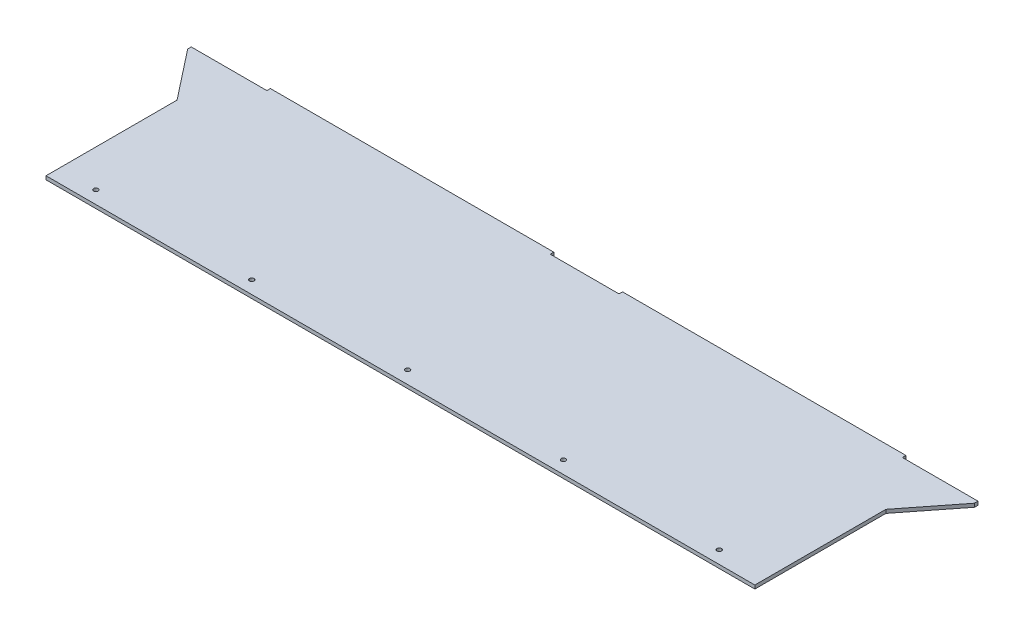
SolidWorks part; units mm, degrees
material "6061-T6 (SS)"
ref_plane "X-Y Datum" through (0, 0, 0) normal (0, 0, 1) x (1, 0, 0)
ref_plane "X-Z Datum" through (0, 0, 0) normal (0, 1, 0) x (1, 0, 0)
ref_plane "Y-Z Datum" through (0, 0, 0) normal (1, 0, 0) x (0, 0, -1)
sketch "Sketch1" plane through (0, 0, 0) normal (0, 1, 0) x (1, 0, 0)
  line L1 (-317.6778, 82.55) -> (317.6778, 82.55)
  line L2 (-317.6778, 82.55) -> (-317.6778, -82.55)
  line L3 (-317.6778, -82.55) -> (317.6778, -82.55)
  line L4 (317.6778, 82.55) -> (317.6778, -82.55)
  line L5 (-317.6778, 82.55) -> (317.6778, -82.55) construction
  line L6 (-317.6778, -82.55) -> (317.6778, 82.55) construction
  point P0 (0, 0)
  dimension "D1" = 635.3556
  dimension "D2" = 165.1
extrude "Boss-Extrude1" add sketch "Sketch1" along normal mid plane 3.175
sketch "Sketch2" plane through (0, 0, -82.55) normal (0, 0, -1) x (-1, 0, 0)
  line L20 (-317.6778, -1.5875) -> (317.6778, -1.5875) construction
  line L21 (-284.8229, -1.5875) -> (-30.8229, -1.5875)
  line L22 (30.8229, -1.5875) -> (284.8229, -1.5875)
  line L40 (30.8229, -1.5875) -> (30.8229, 1.5875)
  line L41 (30.8229, 1.5875) -> (284.8229, 1.5875)
  line L42 (284.8229, 1.5875) -> (284.8229, -1.5875)
  line L56 (-284.8229, -1.5875) -> (-284.8229, 1.5875)
  line L57 (-284.8229, 1.5875) -> (-30.8229, 1.5875)
  line L58 (-30.8229, 1.5875) -> (-30.8229, -1.5875)
extrude "Boss-Extrude2" add sketch "Sketch2" along normal blind 3.175
sketch "Sketch3" plane through (0, -1.5875, 0) normal (0, -1, 0) x (1, 0, 0)
  line L0 (317.6778, -82.55) -> (352.6028, -82.55)
  line L1 (352.6028, -82.55) -> (352.6028, -79.375)
  line L3 (352.6028, -79.375) -> (317.6778, -34.925)
  line L4 (317.6778, 82.55) -> (317.6778, -82.55) construction
  line L17 (317.6778, -82.55) -> (317.6778, 82.55)
  line L18 (317.6778, 82.55) -> (-317.6778, 82.55)
  line L19 (-317.6778, 82.55) -> (-317.6778, -82.55)
  line L20 (-317.6778, -82.55) -> (-284.8229, -82.55)
  line L21 (-284.8229, -82.55) -> (-284.8229, -85.725)
  line L22 (-284.8229, -85.725) -> (-30.8229, -85.725)
  line L23 (-30.8229, -85.725) -> (-30.8229, -82.55)
  line L24 (-30.8229, -82.55) -> (30.8229, -82.55)
  line L25 (30.8229, -82.55) -> (30.8229, -85.725)
  line L26 (30.8229, -85.725) -> (284.8229, -85.725)
  line L27 (284.8229, -85.725) -> (284.8229, -82.55)
  line L28 (284.8229, -82.55) -> (317.6778, -82.55)
  line L29 (317.6778, -82.55) -> (317.6778, -34.925)
  dimension "D1" = 34.925
  dimension "D2" = 3.175
  dimension "D3" = 44.45
  dimension "D4" = 0
extrude "Boss-Extrude3" add sketch "Sketch3" against normal blind 3.175
mirror "Mirror1" about plane through (0, 0, 0) normal (1, 0, 0) of "Boss-Extrude3"
sketch "Sketch4" plane through (0, -1.5875, 0) normal (0, -1, 0) x (1, 0, 0)
  line L0 (-284.4038, 82.55) -> (-284.4038, 71.12)
  line L1 (-317.6778, 82.55) -> (317.6778, 82.55) construction
  line L2 (-284.4038, 71.12) -> (-317.6778, 71.12)
  line L3 (-317.6778, -34.925) -> (-317.6778, 82.55) construction
  circle A0 centre (-284.4038, 71.12) radius 2.025
extrude "Cut-Extrude1" cut sketch "Sketch4" against normal through all contours L2 A0 L0 | L0 A0 L2 region at (-284.1173, -1.5875, 70.8335) region at (-285.2632, -1.5875, 71.9794)
pattern_linear "LPattern1" count 5 spacing 139.7 along (1, 0, 0) of "Cut-Extrude1"
